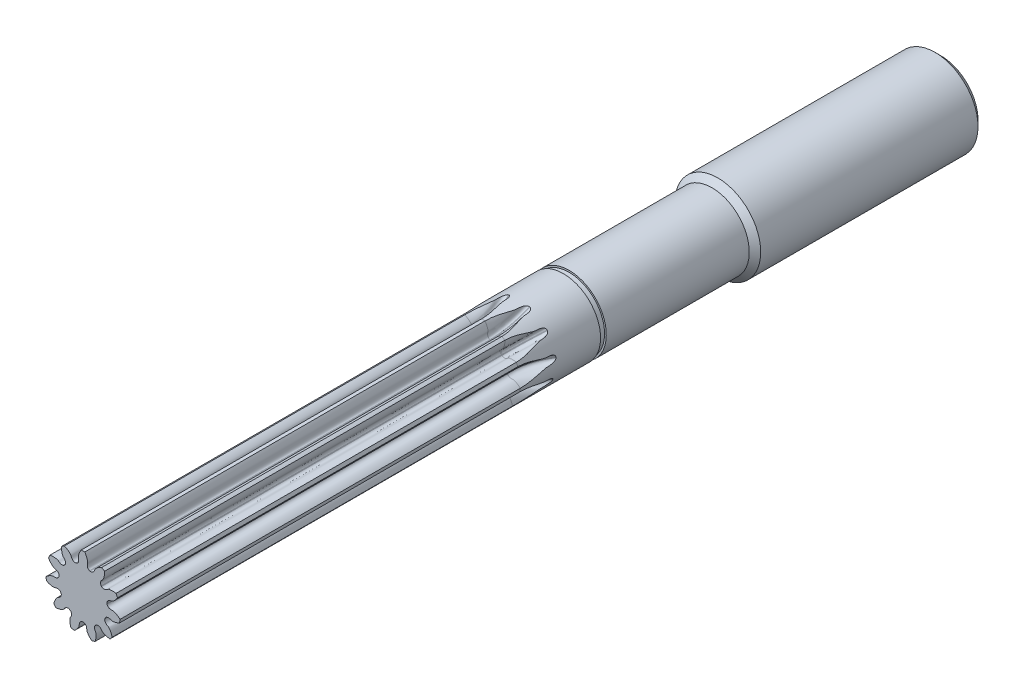
SolidWorks part; units mm, degrees
ref_plane "Спереди" through (0, 0, 0) normal (0, 0, 1) x (1, 0, 0)
ref_plane "Сверху" through (0, 0, 0) normal (0, 1, 0) x (1, 0, 0)
ref_plane "Справа" through (0, 0, 0) normal (1, 0, 0) x (0, 0, -1)
other "Configuration Table"
sketch "Эскиз1" plane through (0, 0, 0) normal (0, 0, 1) x (1, 0, 0)
  line L0 (0, 4.2505) -> (0, 6.5001) construction
  arc A6 (0.303, 6.493) -> (-0.303, 6.493) centre (0, 0) ccw
  arc A8 (3.7653, 5.2984) -> (3.2555, 5.6261) centre (0, 0) ccw
  arc A9 (6.0321, 2.4217) -> (5.7804, 2.9729) centre (0, 0) ccw
  arc A10 (6.3838, -1.224) -> (6.47, -0.6241) centre (0, 0) ccw
  arc A11 (4.7087, -4.481) -> (5.1055, -4.023) centre (0, 0) ccw
  arc A12 (1.5386, -6.3154) -> (2.12, -6.1446) centre (0, 0) ccw
  arc A13 (-2.12, -6.1446) -> (-1.5386, -6.3154) centre (0, 0) ccw
  arc A14 (-5.1055, -4.023) -> (-4.7087, -4.481) centre (0, 0) ccw
  arc A15 (-6.47, -0.6241) -> (-6.3838, -1.224) centre (0, 0) ccw
  arc A16 (-5.7804, 2.9729) -> (-6.0321, 2.4217) centre (0, 0) ccw
  arc A17 (-3.2555, 5.6261) -> (-3.7653, 5.2984) centre (0, 0) ccw
  arc A18 (-4.1999, 0.6538) -> (-4.214, 0.5559) centre (0, 0) ccw
  arc A19 (-3.1797, 2.8207) -> (-3.2445, 2.746) centre (0, 0) ccw
  arc A20 (-1.15, 4.092) -> (-1.2449, 4.0641) centre (0, 0) ccw
  arc A21 (1.2449, 4.0641) -> (1.15, 4.092) centre (0, 0) ccw
  arc A22 (3.2445, 2.746) -> (3.1797, 2.8207) centre (0, 0) ccw
  arc A23 (4.214, 0.5559) -> (4.1999, 0.6538) centre (0, 0) ccw
  arc A24 (3.8456, -1.8106) -> (3.8867, -1.7206) centre (0, 0) ccw
  arc A25 (2.2563, -3.6023) -> (2.3394, -3.5488) centre (0, 0) ccw
  arc A26 (-0.0494, -4.2502) -> (0.0494, -4.2502) centre (0, 0) ccw
  arc A27 (-2.3394, -3.5488) -> (-2.2563, -3.6023) centre (0, 0) ccw
  arc A28 (-3.8867, -1.7206) -> (-3.8456, -1.8106) centre (0, 0) ccw
  spline S0 degree 3 poles (0.303, 6.493) (0.3466, 6.4296) (0.4149, 6.3229) (0.5038, 6.1711) (0.5716, 6.0406) (0.6313, 5.9095) (0.6852, 5.7791) (0.7296, 5.6484) (0.7674, 5.5183) (0.798, 5.3728) (0.8278, 5.1961) (0.7682, 4.9723) (0.7367, 4.7556) (0.754, 4.5684) (0.7852, 4.4471) (0.829, 4.3517) (0.8776, 4.2755) (0.9328, 4.2146) (1.0177, 4.1438) (1.0937, 4.1064) (1.15, 4.092) knots 0 0 0 0 0.085617 0.14097 0.195721 0.24917 0.301247 0.352629 0.402768 0.451734 0.518548 0.599046 0.705842 0.760988 0.807057 0.844573 0.877292 0.907236 0.935686 1 1 1 1
  spline S1 degree 3 poles (-0.303, 6.493) (-0.3466, 6.4296) (-0.4149, 6.3229) (-0.5038, 6.1711) (-0.5716, 6.0406) (-0.6313, 5.9095) (-0.6852, 5.7791) (-0.7296, 5.6484) (-0.7674, 5.5183) (-0.798, 5.3728) (-0.8278, 5.1961) (-0.7682, 4.9723) (-0.7367, 4.7556) (-0.754, 4.5684) (-0.7852, 4.4471) (-0.829, 4.3517) (-0.8776, 4.2755) (-0.9328, 4.2146) (-1.0177, 4.1438) (-1.0937, 4.1064) (-1.15, 4.092) knots 0 0 0 0 0.085617 0.14097 0.195721 0.24917 0.301247 0.352629 0.402768 0.451734 0.518548 0.599046 0.705842 0.760988 0.807057 0.844573 0.877292 0.907236 0.935686 1 1 1 1
  spline S2 degree 3 poles (3.2555, 5.6261) (3.1845, 5.5963) (3.0694, 5.5435) (2.9125, 5.4638) (2.7849, 5.3907) (2.6639, 5.3126) (2.548, 5.2321) (2.4399, 5.1462) (2.3379, 5.0572) (2.2335, 4.9513) (2.1128, 4.8187) (2.042, 4.5983) (1.9513, 4.399) (1.8356, 4.2508) (1.7437, 4.1657) (1.6553, 4.1091) (1.5733, 4.0713) (1.4939, 4.0498) (1.3841, 4.0362) (1.3, 4.0458) (1.2449, 4.0641) knots 0 0 0 0 0.085617 0.14097 0.195721 0.24917 0.301247 0.352629 0.402768 0.451734 0.518548 0.599046 0.705842 0.760988 0.807057 0.844573 0.877292 0.907236 0.935686 1 1 1 1
  spline S3 degree 3 poles (3.7653, 5.2984) (3.7677, 5.2215) (3.7674, 5.0948) (3.7602, 4.9191) (3.7467, 4.7726) (3.7259, 4.6301) (3.7008, 4.4913) (3.6676, 4.3573) (3.629, 4.2274) (3.5761, 4.0885) (3.5056, 3.9237) (3.3345, 3.7676) (3.1908, 3.6024) (3.1041, 3.4356) (3.0649, 3.3166) (3.0502, 3.2127) (3.0498, 3.1224) (3.0633, 3.0412) (3.0965, 2.9357) (3.1402, 2.8632) (3.1797, 2.8207) knots 0 0 0 0 0.085617 0.14097 0.195721 0.24917 0.301247 0.352629 0.402768 0.451734 0.518548 0.599046 0.705842 0.760988 0.807057 0.844573 0.877292 0.907236 0.935686 1 1 1 1
  spline S4 degree 3 poles (5.7804, 2.9729) (5.7046, 2.9862) (5.5791, 3.004) (5.4041, 3.0219) (5.2573, 3.0293) (5.1132, 3.0291) (4.9722, 3.024) (4.8349, 3.0101) (4.7009, 2.9904) (4.5558, 2.9578) (4.3826, 2.9115) (4.2038, 2.7644) (4.0198, 2.6457) (3.8424, 2.5836) (3.719, 2.5617) (3.6141, 2.5619) (3.5246, 2.5744) (3.4462, 2.5993) (3.3465, 2.6472) (3.281, 2.7007) (3.2445, 2.746) knots 0 0 0 0 0.085617 0.14097 0.195721 0.24917 0.301247 0.352629 0.402768 0.451734 0.518548 0.599046 0.705842 0.760988 0.807057 0.844573 0.877292 0.907236 0.935686 1 1 1 1
  spline S5 degree 3 poles (6.0321, 2.4217) (5.9925, 2.3557) (5.9238, 2.2492) (5.8227, 2.1053) (5.7322, 1.9894) (5.6377, 1.8807) (5.5415, 1.7775) (5.4411, 1.6827) (5.3384, 1.5943) (5.2188, 1.5061) (5.0704, 1.4055) (4.8421, 1.3668) (4.6319, 1.3054) (4.4688, 1.212) (4.3714, 1.1331) (4.3029, 1.0537) (4.2537, 0.9778) (4.2212, 0.9023) (4.1921, 0.7956) (4.1897, 0.711) (4.1999, 0.6538) knots 0 0 0 0 0.085617 0.14097 0.195721 0.24917 0.301247 0.352629 0.402768 0.451734 0.518548 0.599046 0.705842 0.760988 0.807057 0.844573 0.877292 0.907236 0.935686 1 1 1 1
  spline S6 degree 3 poles (6.47, -0.6241) (6.4135, -0.572) (6.3176, -0.4892) (6.18, -0.3795) (6.0605, -0.2938) (5.9391, -0.2162) (5.8178, -0.1442) (5.6948, -0.0816) (5.5714, -0.0258) (5.4317, 0.0252) (5.261, 0.0799) (5.031, 0.0528) (4.812, 0.0524) (4.6292, 0.0961) (4.5136, 0.1444) (4.4254, 0.2013) (4.3569, 0.2602) (4.3044, 0.3235) (4.2465, 0.4177) (4.2203, 0.4982) (4.214, 0.5559) knots 0 0 0 0 0.085617 0.14097 0.195721 0.24917 0.301247 0.352629 0.402768 0.451734 0.518548 0.599046 0.705842 0.760988 0.807057 0.844573 0.877292 0.907236 0.935686 1 1 1 1
  spline S7 degree 3 poles (6.3838, -1.224) (6.3148, -1.2581) (6.1995, -1.3105) (6.0366, -1.3769) (5.8978, -1.4255) (5.7595, -1.4658) (5.6228, -1.5007) (5.4871, -1.5261) (5.3529, -1.5449) (5.2046, -1.5545) (5.0254, -1.5588) (4.8124, -1.468) (4.6023, -1.406) (4.4146, -1.3964) (4.2901, -1.4101) (4.1895, -1.4399) (4.1071, -1.4771) (4.0389, -1.5231) (3.9568, -1.5971) (3.909, -1.667) (3.8867, -1.7206) knots 0 0 0 0 0.085617 0.14097 0.195721 0.24917 0.301247 0.352629 0.402768 0.451734 0.518548 0.599046 0.705842 0.760988 0.807057 0.844573 0.877292 0.907236 0.935686 1 1 1 1
  spline S8 degree 3 poles (5.1055, -4.023) (5.0861, -3.9486) (5.0502, -3.827) (4.9937, -3.6604) (4.9395, -3.5237) (4.8795, -3.3928) (4.8163, -3.2667) (4.7466, -3.1475) (4.673, -3.0338) (4.5831, -2.9154) (4.469, -2.7771) (4.2609, -2.6756) (4.0765, -2.5575) (3.9463, -2.4219) (3.8751, -2.3188) (3.8317, -2.2233) (3.8059, -2.1366) (3.796, -2.055) (3.7981, -1.9445) (3.8196, -1.8626) (3.8456, -1.8106) knots 0 0 0 0 0.085617 0.14097 0.195721 0.24917 0.301247 0.352629 0.402768 0.451734 0.518548 0.599046 0.705842 0.760988 0.807057 0.844573 0.877292 0.907236 0.935686 1 1 1 1
  spline S9 degree 3 poles (4.7087, -4.481) (4.6322, -4.4724) (4.5068, -4.4542) (4.3339, -4.422) (4.1908, -4.3878) (4.0527, -4.3469) (3.9189, -4.3023) (3.791, -4.2503) (3.6679, -4.1937) (3.538, -4.1215) (3.3848, -4.0283) (3.2547, -3.8367) (3.1116, -3.671) (2.9588, -3.5615) (2.8467, -3.5057) (2.7459, -3.4763) (2.6565, -3.4631) (2.5743, -3.4649) (2.4652, -3.4828) (2.3872, -3.5157) (2.3394, -3.5488) knots 0 0 0 0 0.085617 0.14097 0.195721 0.24917 0.301247 0.352629 0.402768 0.451734 0.518548 0.599046 0.705842 0.760988 0.807057 0.844573 0.877292 0.907236 0.935686 1 1 1 1
  spline S10 degree 3 poles (2.12, -6.1446) (2.144, -6.0715) (2.1795, -5.9499) (2.222, -5.7792) (2.2503, -5.6349) (2.2706, -5.4922) (2.2856, -5.352) (2.2914, -5.214) (2.291, -5.0786) (2.2793, -4.9304) (2.2582, -4.7524) (2.138, -4.5545) (2.0467, -4.3554) (2.0105, -4.1709) (2.0063, -4.0457) (2.0215, -3.9419) (2.0466, -3.8551) (2.0824, -3.7811) (2.144, -3.6892) (2.2063, -3.6319) (2.2563, -3.6023) knots 0 0 0 0 0.085617 0.14097 0.195721 0.24917 0.301247 0.352629 0.402768 0.451734 0.518548 0.599046 0.705842 0.760988 0.807057 0.844573 0.877292 0.907236 0.935686 1 1 1 1
  spline S11 degree 3 poles (1.5386, -6.3154) (1.4789, -6.2668) (1.3833, -6.1836) (1.2552, -6.0631) (1.1533, -5.957) (1.0592, -5.8479) (0.9707, -5.738) (0.8913, -5.6252) (0.8184, -5.511) (0.7481, -5.38) (0.6696, -5.2188) (0.6638, -4.9873) (0.6329, -4.7705) (0.5636, -4.5958) (0.4995, -4.4882) (0.4306, -4.409) (0.3625, -4.3496) (0.2924, -4.3067) (0.1909, -4.2627) (0.1075, -4.2482) (0.0494, -4.2502) knots 0 0 0 0 0.085617 0.14097 0.195721 0.24917 0.301247 0.352629 0.402768 0.451734 0.518548 0.599046 0.705842 0.760988 0.807057 0.844573 0.877292 0.907236 0.935686 1 1 1 1
  spline S12 degree 3 poles (-1.5386, -6.3154) (-1.4789, -6.2668) (-1.3833, -6.1836) (-1.2552, -6.0631) (-1.1533, -5.957) (-1.0592, -5.8479) (-0.9707, -5.738) (-0.8913, -5.6252) (-0.8184, -5.511) (-0.7481, -5.38) (-0.6696, -5.2188) (-0.6638, -4.9873) (-0.6329, -4.7705) (-0.5636, -4.5958) (-0.4995, -4.4882) (-0.4306, -4.409) (-0.3625, -4.3496) (-0.2924, -4.3067) (-0.1909, -4.2627) (-0.1075, -4.2482) (-0.0494, -4.2502) knots 0 0 0 0 0.085617 0.14097 0.195721 0.24917 0.301247 0.352629 0.402768 0.451734 0.518548 0.599046 0.705842 0.760988 0.807057 0.844573 0.877292 0.907236 0.935686 1 1 1 1
  spline S13 degree 3 poles (-2.12, -6.1446) (-2.144, -6.0715) (-2.1795, -5.9499) (-2.222, -5.7792) (-2.2503, -5.6349) (-2.2706, -5.4922) (-2.2856, -5.352) (-2.2914, -5.214) (-2.291, -5.0786) (-2.2793, -4.9304) (-2.2582, -4.7524) (-2.138, -4.5545) (-2.0467, -4.3554) (-2.0105, -4.1709) (-2.0063, -4.0457) (-2.0215, -3.9419) (-2.0466, -3.8551) (-2.0824, -3.7811) (-2.144, -3.6892) (-2.2063, -3.6319) (-2.2563, -3.6023) knots 0 0 0 0 0.085617 0.14097 0.195721 0.24917 0.301247 0.352629 0.402768 0.451734 0.518548 0.599046 0.705842 0.760988 0.807057 0.844573 0.877292 0.907236 0.935686 1 1 1 1
  spline S14 degree 3 poles (-4.7087, -4.481) (-4.6322, -4.4724) (-4.5068, -4.4542) (-4.3339, -4.422) (-4.1908, -4.3878) (-4.0527, -4.3469) (-3.9189, -4.3023) (-3.791, -4.2503) (-3.6679, -4.1937) (-3.538, -4.1215) (-3.3848, -4.0283) (-3.2547, -3.8367) (-3.1116, -3.671) (-2.9588, -3.5615) (-2.8467, -3.5057) (-2.7459, -3.4763) (-2.6565, -3.4631) (-2.5743, -3.4649) (-2.4652, -3.4828) (-2.3872, -3.5157) (-2.3394, -3.5488) knots 0 0 0 0 0.085617 0.14097 0.195721 0.24917 0.301247 0.352629 0.402768 0.451734 0.518548 0.599046 0.705842 0.760988 0.807057 0.844573 0.877292 0.907236 0.935686 1 1 1 1
  spline S15 degree 3 poles (-5.1055, -4.023) (-5.0861, -3.9486) (-5.0502, -3.827) (-4.9937, -3.6604) (-4.9395, -3.5237) (-4.8795, -3.3928) (-4.8163, -3.2667) (-4.7466, -3.1475) (-4.673, -3.0338) (-4.5831, -2.9154) (-4.469, -2.7771) (-4.2609, -2.6756) (-4.0765, -2.5575) (-3.9463, -2.4219) (-3.8751, -2.3188) (-3.8317, -2.2233) (-3.8059, -2.1366) (-3.796, -2.055) (-3.7981, -1.9445) (-3.8196, -1.8626) (-3.8456, -1.8106) knots 0 0 0 0 0.085617 0.14097 0.195721 0.24917 0.301247 0.352629 0.402768 0.451734 0.518548 0.599046 0.705842 0.760988 0.807057 0.844573 0.877292 0.907236 0.935686 1 1 1 1
  spline S16 degree 3 poles (-6.3838, -1.224) (-6.3148, -1.2581) (-6.1995, -1.3105) (-6.0366, -1.3769) (-5.8978, -1.4255) (-5.7595, -1.4658) (-5.6228, -1.5007) (-5.4871, -1.5261) (-5.3529, -1.5449) (-5.2046, -1.5545) (-5.0254, -1.5588) (-4.8124, -1.468) (-4.6023, -1.406) (-4.4146, -1.3964) (-4.2901, -1.4101) (-4.1895, -1.4399) (-4.1071, -1.4771) (-4.0389, -1.5231) (-3.9568, -1.5971) (-3.909, -1.667) (-3.8867, -1.7206) knots 0 0 0 0 0.085617 0.14097 0.195721 0.24917 0.301247 0.352629 0.402768 0.451734 0.518548 0.599046 0.705842 0.760988 0.807057 0.844573 0.877292 0.907236 0.935686 1 1 1 1
  spline S17 degree 3 poles (-6.47, -0.6241) (-6.4135, -0.572) (-6.3176, -0.4892) (-6.18, -0.3795) (-6.0605, -0.2938) (-5.9391, -0.2162) (-5.8178, -0.1442) (-5.6948, -0.0816) (-5.5714, -0.0258) (-5.4317, 0.0252) (-5.261, 0.0799) (-5.031, 0.0528) (-4.812, 0.0524) (-4.6292, 0.0961) (-4.5136, 0.1444) (-4.4254, 0.2013) (-4.3569, 0.2602) (-4.3044, 0.3235) (-4.2465, 0.4177) (-4.2203, 0.4982) (-4.214, 0.5559) knots 0 0 0 0 0.085617 0.14097 0.195721 0.24917 0.301247 0.352629 0.402768 0.451734 0.518548 0.599046 0.705842 0.760988 0.807057 0.844573 0.877292 0.907236 0.935686 1 1 1 1
  spline S18 degree 3 poles (-6.0321, 2.4217) (-5.9925, 2.3557) (-5.9238, 2.2492) (-5.8227, 2.1053) (-5.7322, 1.9894) (-5.6377, 1.8807) (-5.5415, 1.7775) (-5.4411, 1.6827) (-5.3384, 1.5943) (-5.2188, 1.5061) (-5.0704, 1.4055) (-4.8421, 1.3668) (-4.6319, 1.3054) (-4.4688, 1.212) (-4.3714, 1.1331) (-4.3029, 1.0537) (-4.2537, 0.9778) (-4.2212, 0.9023) (-4.1921, 0.7956) (-4.1897, 0.711) (-4.1999, 0.6538) knots 0 0 0 0 0.085617 0.14097 0.195721 0.24917 0.301247 0.352629 0.402768 0.451734 0.518548 0.599046 0.705842 0.760988 0.807057 0.844573 0.877292 0.907236 0.935686 1 1 1 1
  spline S19 degree 3 poles (-5.7804, 2.9729) (-5.7046, 2.9862) (-5.5791, 3.004) (-5.4041, 3.0219) (-5.2573, 3.0293) (-5.1132, 3.0291) (-4.9722, 3.024) (-4.8349, 3.0101) (-4.7009, 2.9904) (-4.5558, 2.9578) (-4.3826, 2.9115) (-4.2038, 2.7644) (-4.0198, 2.6457) (-3.8424, 2.5836) (-3.719, 2.5617) (-3.6141, 2.5619) (-3.5246, 2.5744) (-3.4462, 2.5993) (-3.3465, 2.6472) (-3.281, 2.7007) (-3.2445, 2.746) knots 0 0 0 0 0.085617 0.14097 0.195721 0.24917 0.301247 0.352629 0.402768 0.451734 0.518548 0.599046 0.705842 0.760988 0.807057 0.844573 0.877292 0.907236 0.935686 1 1 1 1
  spline S20 degree 3 poles (-3.7653, 5.2984) (-3.7677, 5.2215) (-3.7674, 5.0948) (-3.7602, 4.9191) (-3.7467, 4.7726) (-3.7259, 4.6301) (-3.7008, 4.4913) (-3.6676, 4.3573) (-3.629, 4.2274) (-3.5761, 4.0885) (-3.5056, 3.9237) (-3.3345, 3.7676) (-3.1908, 3.6024) (-3.1041, 3.4356) (-3.0649, 3.3166) (-3.0502, 3.2127) (-3.0498, 3.1224) (-3.0633, 3.0412) (-3.0965, 2.9357) (-3.1402, 2.8632) (-3.1797, 2.8207) knots 0 0 0 0 0.085617 0.14097 0.195721 0.24917 0.301247 0.352629 0.402768 0.451734 0.518548 0.599046 0.705842 0.760988 0.807057 0.844573 0.877292 0.907236 0.935686 1 1 1 1
  spline S21 degree 3 poles (-3.2555, 5.6261) (-3.1845, 5.5963) (-3.0694, 5.5435) (-2.9125, 5.4638) (-2.7849, 5.3907) (-2.6639, 5.3126) (-2.548, 5.2321) (-2.4399, 5.1462) (-2.3379, 5.0572) (-2.2335, 4.9513) (-2.1128, 4.8187) (-2.042, 4.5983) (-1.9513, 4.399) (-1.8356, 4.2508) (-1.7437, 4.1657) (-1.6553, 4.1091) (-1.5733, 4.0713) (-1.4939, 4.0498) (-1.3841, 4.0362) (-1.3, 4.0458) (-1.2449, 4.0641) knots 0 0 0 0 0.085617 0.14097 0.195721 0.24917 0.301247 0.352629 0.402768 0.451734 0.518548 0.599046 0.705842 0.760988 0.807057 0.844573 0.877292 0.907236 0.935686 1 1 1 1
  point P469 (0, 0)
  point P490 (0, 0)
  dimension "D1" = 11
  dimension "D2" = 11
extrude "Бобышка-Вытянуть1" add sketch "Эскиз1" along normal blind 70
sketch "Эскиз3" plane through (0, 0, 0) normal (1, 0, 0) x (0, 0, -1)
  line L1 (0, 50) -> (0, -50) construction
  line L2 (40, 6.5) -> (40, 7.5)
  line L3 (40, 7.5) -> (80, 7.5)
  line L4 (80, 7.5) -> (80, 0)
  line L5 (80, 0) -> (0, 0)
  line L6 (0, 0) -> (0, 6.5)
  line L7 (0, 6.5) -> (14, 6.5)
  line L8 (14, 6.5) -> (14, 6.2)
  line L9 (14, 6.2) -> (15, 6.2)
  line L10 (15, 6.2) -> (15, 6.5)
  line L11 (15, 6.5) -> (40, 6.5)
  dimension "D1" = 80
  dimension "D2" = 25
  dimension "D3" = 40
  dimension "D4" = 7.5
  dimension "D5" = 1
  dimension "D6" = 0.3
  dimension "D7" = 6.5
  dimension "D8" = 6.5
revolve "Повернуть1" add sketch "Эскиз3" angle 360 about L5
chamfer "Фаска1" distance 1 angle 45 2 edges at (0, 7.5, -40) (0, 7.5, -80)
sketch "Эскиз5" plane through (0, 0, 0) normal (0, 0, 1) x (1, 0, 0)
  line L9 (2.4864, 13.9291) -> (6.4361, 12.7693) construction
  arc A1 (4.6682, 5.8701) -> (-0.7535, 7.4621) centre (0, 0) ccw
  arc A2 (-0.7535, 7.4621) -> (0.303, 6.493) centre (3.1196, 10.6242) ccw
  arc A3 (3.2555, 5.6261) -> (4.6682, 5.8701) centre (3.1196, 10.6242) ccw
  arc A4 (1.15, 4.092) -> (1.2449, 4.0641) centre (0, 0) cw
  arc A6 (1.2449, 4.0641) -> (1.15, 4.092) centre (0, 0) ccw construction
  spline S0 degree 3 poles (1.15, 4.092) (1.0937, 4.1064) (1.0177, 4.1438) (0.9328, 4.2146) (0.8776, 4.2755) (0.829, 4.3517) (0.7852, 4.4471) (0.754, 4.5684) (0.7367, 4.7556) (0.7682, 4.9723) (0.8278, 5.1961) (0.798, 5.3728) (0.7674, 5.5183) (0.7296, 5.6484) (0.6852, 5.7791) (0.6313, 5.9095) (0.5716, 6.0406) (0.5038, 6.1711) (0.4149, 6.3229) (0.3466, 6.4296) (0.303, 6.493) knots 0 0 0 0 0.064314 0.092764 0.122708 0.155427 0.192943 0.239012 0.294158 0.400954 0.481452 0.548266 0.597232 0.647371 0.698753 0.75083 0.804279 0.85903 0.914383 1 1 1 1
  spline S1 degree 3 poles (1.2449, 4.0641) (1.3, 4.0458) (1.3841, 4.0362) (1.4939, 4.0498) (1.5733, 4.0713) (1.6553, 4.1091) (1.7437, 4.1657) (1.8356, 4.2508) (1.9513, 4.399) (2.042, 4.5983) (2.1128, 4.8187) (2.2335, 4.9513) (2.3379, 5.0572) (2.4399, 5.1462) (2.548, 5.2321) (2.6639, 5.3126) (2.7849, 5.3907) (2.9125, 5.4638) (3.0694, 5.5435) (3.1845, 5.5963) (3.2555, 5.6261) knots 0 0 0 0 0.064314 0.092764 0.122708 0.155427 0.192943 0.239012 0.294158 0.400954 0.481452 0.548266 0.597232 0.647371 0.698753 0.75083 0.804279 0.85903 0.914383 1 1 1 1
  dimension "D1" = 10.6242
  dimension "D2" = 15
revolve "Вырез-Повернуть1" cut sketch "Эскиз5" angle 360 about L9
pattern_circular "Круговой массив1" count 11 over 360 about axis through (0, 0, -80) along (0, 0, -1) of "Вырез-Повернуть1" reverse direction yes
